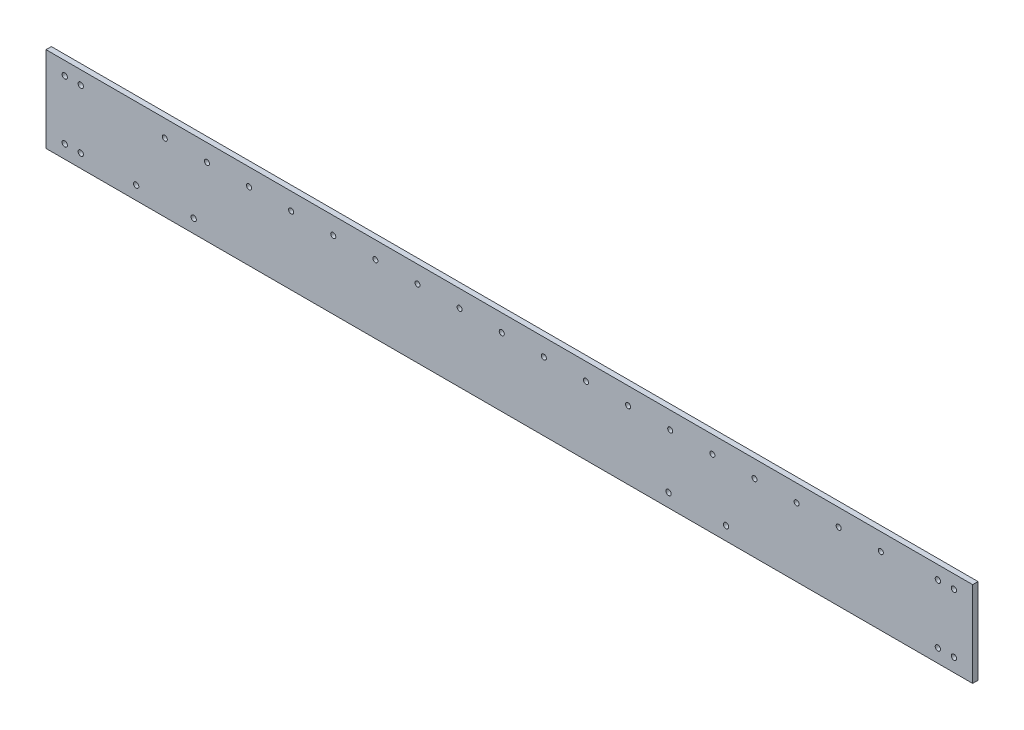
SolidWorks part; units mm, degrees
ref_plane "Front Plane" through (0, 0, 0) normal (0, 0, 1) x (1, 0, 0)
ref_plane "Top Plane" through (0, 0, 0) normal (0, 1, 0) x (1, 0, 0)
ref_plane "Right Plane" through (0, 0, 0) normal (1, 0, 0) x (0, 0, -1)
sketch "Sketch1" plane through (0, 0, 0) normal (1, 0, 0) x (0, 0, -1)
  line L0 (0, 0) -> (-3.175, 0)
  line L3 (-3.175, 0) -> (-3.175, 50.8)
  line L4 (-3.175, 50.8) -> (0, 50.8)
  line L5 (0, 50.8) -> (0, 0)
  dimension "LHeight" = 50.8
  dimension "LMaterialThickness" = 3.175
extrude "Boss-Extrude1" add sketch "Sketch1" along normal blind 550
sketch "LeftSideHoles-Sketch4" plane through (0, 0, 3.175) normal (0, 0, 1) x (1, 0, 0)
  line L0 (550, 50.8) -> (550, 0) construction
  line L1 (0, 50.8) -> (0, 0) construction
  line L2 (550, 50.8) -> (550, 0) construction
  line L3 (550, 50.8) -> (0, 50.8) construction
  line L4 (550, 0) -> (0, 0) construction
  line L5 (550, 50.8) -> (0, 50.8) construction
  line L6 (0, 50.8) -> (0, 0) construction
  circle A1 centre (11.1125, 42.8625) radius 1.5875
  circle A3 centre (529.3625, 42.8625) radius 1.5875
  circle A4 centre (20.6375, 42.8625) radius 1.5875
  circle A5 centre (538.8875, 42.8625) radius 1.5875
  circle A6 centre (11.1125, 7.9375) radius 1.5875
  circle A7 centre (20.6375, 7.9375) radius 1.5875
  circle A8 centre (529.3625, 7.9375) radius 1.5875
  circle A9 centre (538.8875, 7.9375) radius 1.5875
  circle A10 centre (495.5, 40.575) radius 1.5
  circle A11 centre (470.5, 40.575) radius 1.5
  circle A12 centre (445.5, 40.575) radius 1.5
  circle A13 centre (420.5, 40.575) radius 1.5
  circle A14 centre (395.5, 40.575) radius 1.5
  circle A15 centre (370.5, 40.575) radius 1.5
  circle A16 centre (345.5, 40.575) radius 1.5
  circle A17 centre (320.5, 40.575) radius 1.5
  circle A18 centre (295.5, 40.575) radius 1.5
  circle A19 centre (270.5, 40.575) radius 1.5
  circle A20 centre (245.5, 40.575) radius 1.5
  circle A21 centre (220.5, 40.575) radius 1.5
  circle A22 centre (195.5, 40.575) radius 1.5
  circle A23 centre (170.5, 40.575) radius 1.5
  circle A24 centre (145.5, 40.575) radius 1.5
  circle A25 centre (120.5, 40.575) radius 1.5
  circle A26 centre (95.5, 40.575) radius 1.5
  circle A27 centre (70.5, 40.575) radius 1.5
  circle A28 centre (53.5125, 7.9375) radius 1.5875
  circle A31 centre (369.5125, 7.9375) radius 1.5875
  circle A33 centre (87.6375, 7.9375) radius 1.5875
  circle A35 centre (403.6375, 7.9375) radius 1.5875
  dimension "D2" = 3.175
  dimension "D10" = 3
  dimension "D14" = 3.175
  dimension "D4" = 7.9375
  dimension "D1" = 11.1125
  dimension "D6" = 20.6375
  dimension "D3" = 11.1125
  dimension "D5" = 20.6375
  dimension "D7" = 7.9375
  dimension "D8" = 54.5
  dimension "D9" = 10.225
  dimension "D12" = 25
  dimension "D13" = 7.9375
  dimension "D15" = 53.5125
  dimension "D17" = 316
  dimension "D20" = 34.125
  dimension "D16" = 34.125
  dimension "D11" = 18
extrude "LeftSideHoles-Cut-Extrude3" cut sketch "LeftSideHoles-Sketch4" against normal through all
equation "\"RailThickness\"= .125in'Spec"
equation "\"SideRailHoleY1FromEdge\"= \"HoleOffsetFromEdge\""
equation "\"SideRailHoleX1FromSide\"= \"HoleOffsetFromSide\""
equation "\"MidSideRailLength\"= \"SideRailLength\""
equation "\"VSWidth\"= 1.25in'Spec"
equation "\"HoleOffsetFromEdge\"= \"RailThickness\" * 2.5"
equation "\"HoleOffsetFromSide\"= \"RailThickness\" * 3.5"
equation "\"SideRailHoleX2FromSide\"= \"VSWidth\" - \"HoleOffsetFromEdge\" - \"RailThickness\"'Equals 20.6375"
equation "\"FasteningHoleDiameter\"= .125in"
equation "\"D2@LeftSideHoles-Sketch4\" = \"FasteningHoleDiameter\""
equation "\"LHeight@Sketch1\"=\"MidLeftOrRightSideRailHeight\""
equation "\"LMaterialThickness@Sketch1\"=\"RailThickness\""
equation "\"D1@Boss-Extrude1\"=\"MidSideRailLength\""
equation "\"D4@LeftSideHoles-Sketch4\" = \"SideRailHoleY1FromEdge\""
equation "\"D1@LeftSideHoles-Sketch4\"=\"SideRailHoleX1FromSide\""
equation "\"D6@LeftSideHoles-Sketch4\"=\"SideRailHoleX2FromSide\" "
equation "\"D3@LeftSideHoles-Sketch4\"=\"SideRailHoleX1FromSide\" "
equation "\"D5@LeftSideHoles-Sketch4\"=\"SideRailHoleX2FromSide\" "
equation "\"D7@LeftSideHoles-Sketch4\"=\"HoleOffsetFromEdge\""
equation "\"LinearRailXMountHole\"= \"StepperWidth\" + \"LinearRailFirstHoleOffsetFromEdge\""
equation "\"D8@LeftSideHoles-Sketch4\"=\"LinearRailXMountHole\""
equation "\"D9@LeftSideHoles-Sketch4\"=\"V6.3 GantryMiddleToTopOfMidSideRail\""
equation "\"LinearRailHoleDistance\"= 25mm'Spec"
equation "\"D12@LeftSideHoles-Sketch4\"=\"LinearRailHoleDistance\""
equation "\"LinearRailFirstHoleOffsetFromEdge\"= 12.5mm'Spec"
equation "\"SideRailLength\"= 550mm"
equation "\"MidLeftOrRightSideRailHeight\"= 2.0in"
equation "\"StepperWidth\"= 42mm'Spec"
equation "\"StepperHolePadSize\"= \"StepperHoleDiameter\""
equation "\"MidRailRodStabilizerMountingHoleOffsetFromEdge\"= \"HoleOffsetFromEdge\""
equation "\"D13@LeftSideHoles-Sketch4\"=\"MidRailRodStabilizerMountingHoleOffsetFromEdge\""
equation "\"D14@LeftSideHoles-Sketch4\"=\"FasteningHoleDiameter\""
equation "\"DistanceFromBedFrontToFirstLeftStepperHole\"= \"LeadScrewNutPadSize\" + 10mm'Equals 34"
equation "\"BeltTensionerDepth\"= \"BeltTensionerBackWallThickness\" + \"BeltTensionerInnerDepth\"'Equals 23.4"
equation "\"20TGT2PulleyDiameter\"= 17.9mm'Spec"
equation "\"BeltTensionerSpaceBetweenPulleyAndWall\"= 1.5mm"
equation "\"BeltTensionerBackWallThickness\"= 4mm"
equation "\"BeltTensionerInnerDepth\"= \"20TGT2PulleyDiameter\" + \"BeltTensionerSpaceBetweenPulleyAndWall\""
equation "\"DistanceFromFrontSideToBedFront\"= \"RailThickness\" + \"BeltTensionerDepth\" + 10mm'Equals 36.575"
equation "\"DistanceFromFrontSideToFirstLeftStepperHole\"= \"DistanceFromFrontSideToBedFront\" + \"DistanceFromBedFrontToFirstLeftStepperHole\"'Equals 70.575"
equation "\"DistanceBetweenFrontToBackStepperHoles\"= \"BedLength\" - \"DistanceFromBedFrontToFirstLeftStepperHole\"'Equals 316"
equation "\"BedLength\"= \"BedInnerSquareLength\" + \"BedLWidth\" * 2 - \"BedOverlap\" * 2 + \"BedIncreasedByLength\"'Equals 350"
equation "\"BedOverlap\"= 20mm"
equation "\"BedThirdSize\"= 70mm"
equation "\"BedInnerSquareWidth\"= \"BedThirdSize\" * 3'Equals 210"
equation "\"BedLWidth\"= \"BedThirdSize\" + \"BedOverlap\"'Equals 90"
equation "\"BedIncreasedByLength\"= 0mm"
equation "\"BedInnerSquareLength\"= \"BedInnerSquareWidth\""
equation "\"DistanceFromFrontSideToFirstLeftRodStabilizerMountingHole\"= \"DistanceFromFrontSideToFirstLeftStepperHole\" - \"DistanceFromStepperHoleToRodStabilizerMountingHole\"'Equals 53.5125"
equation "\"D15@LeftSideHoles-Sketch4\"=\"DistanceFromFrontSideToFirstLeftRodStabilizerMountingHole\""
equation "\"D17@LeftSideHoles-Sketch4\"=\"DistanceBetweenFrontToBackStepperHoles\""
equation "\"GABMidWallHeight\"= 28mm'Must equal 28 or changes alignment"
equation "\"20TGT2PulleyWidth\"= 8.7mm'The STL of the Pulley in the diagram is a bit larger"
equation "\"GABMidShortRiserHeight\"= \"GABMidWallHeight\" / 2 - \"20TGT2PulleyWidth\"'Equals 5.3"
equation "\"GABUpperHeight\"= 6mm"
equation "\"GABLowerHeight\"= 3mm"
equation "\"GABHeight\"= \"GABLowerHeight\" + \"GABMidWallHeight\" + \"GABUpperHeight\""
equation "\"GABRiserBossOffset\"= 0.8mm'Aligns Pulleys"
equation "\"StepperShaftLength\"= 24mm'Pulley will be attached to the end"
equation "\"V6.1 FromGantryPulleyToGantryMiddle\"= \"GABHeight\" / 2 - \"GABMidShortRiserHeight\" - \"GABLowerHeight\" + \"GABRiserBossOffset\" / 2"
equation "\"V6.2 GantryMiddleToTopOfMidBackRail\"= \"StepperShaftLength\" - \"V6.1 FromGantryPulleyToGantryMiddle\""
equation "\"V6.3 GantryMiddleToTopOfMidSideRail\"= \"V6.2 GantryMiddleToTopOfMidBackRail\" - \"RailThickness\""
equation "\"LeadScrewNutMountingHoleFlangeDiameter\"= 22mm'Spec"
equation "\"LeadScrewNutPadSize\"= \"LeadScrewNutMountingHoleFlangeDiameter\" + 2mm'Equals 24"
equation "\"D20@LeftSideHoles-Sketch4\"=\"RodStabilizerLength\" - \"HoleOffsetFromEdge\" * 2"
equation "\"DistanceFromStepperHoleToRodStabilizerMountingHole\"= \"RodStabilizerLength\" / 2 - \"HoleOffsetFromEdge\"'Equals 17.0625"
equation "\"RodStabilizerLength\"= 50mm"
equation "\"D16@LeftSideHoles-Sketch4\"=\"RodStabilizerLength\" - \"HoleOffsetFromEdge\" * 2"
